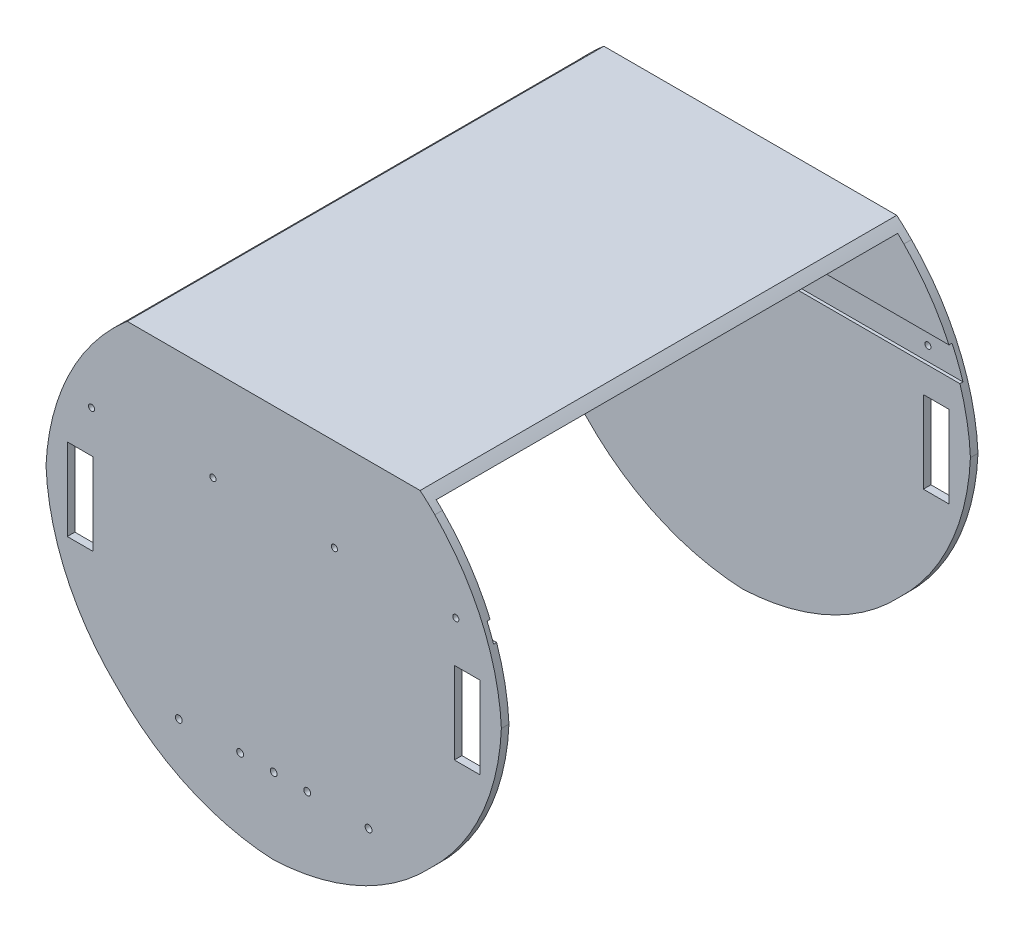
SolidWorks part; units mm, degrees
material "ABS"
ref_plane "Front Plane" through (0, 0, 0) normal (0, 0, 1) x (1, 0, 0)
ref_plane "Top Plane" through (0, 0, 0) normal (0, 1, 0) x (1, 0, 0)
ref_plane "Right Plane" through (0, 0, 0) normal (1, 0, 0) x (0, 0, -1)
sketch "Sketch1" plane through (0, 0, 0) normal (1, 0, 0) x (0, 0, -1)
  line L0 (-152, 0) -> (152, 0) construction
  line L1 (-152, 0) -> (-152, 254)
  line L2 (-152, 254) -> (152, 254)
  line L3 (152, 254) -> (152, 0)
  line L5 (-157, 0) -> (-157, 259)
  line L6 (-157, 259) -> (157, 259)
  line L7 (157, 259) -> (157, 0)
  line L8 (157, 0) -> (152, 0)
  line L10 (-152, 0) -> (-157, 0)
  point P4 (0, 0)
  dimension "D1" = 304
  dimension "D2" = 5
  dimension "D3" = 5
  dimension "D4" = 5
  dimension "D7" = 254
extrude "Boss-Extrude1" add sketch "Sketch1" along normal blind 150 and the other way blind 150
sketch "Sketch2" plane through (0, 0, 0) normal (0, 0, 1) x (1, 0, 0)
  line L1 (0, 150) -> (0, 0) construction
  line L2 (0, 150) -> (150, 150) construction
  line L3 (0, 150) -> (103.1245, 46.8755) construction
  line L4 (0, 150) -> (56.5109, 13.5707) construction
  line L5 (0, 150) -> (136.4293, 93.4891) construction
  line L6 (56.5109, 13.5707) -> (0, 13.5707) construction
  line L7 (136.4293, 93.4891) -> (136.4293, 150) construction
  line L8 (0, 150) -> (131.304, 216.3149) construction
  line L9 (0, 150) -> (0, 295.5) construction
  line L10 (0, 150) -> (106.1806, 249.9895) construction
  arc A0 (0, 0) -> (103.1245, 46.8755) centre (-6.3266, 150.7909) ccw
  arc A1 (150, 150) -> (103.1245, 46.8755) centre (-0.7909, 156.3266) cw
  arc A2 (106.1806, 249.9895) -> (150, 150) centre (-2.2818, 142.8605) cw
  arc A3 (106.1806, 249.9895) -> (0, 295.5) centre (-2.7988, 142.3499) ccw
  arc A4 (0, 0) -> (-103.1245, 46.8755) centre (6.3266, 150.7909) cw
  arc A5 (-150, 150) -> (-103.1245, 46.8755) centre (0.7909, 156.3266) ccw
  arc A6 (-106.1806, 249.9895) -> (-150, 150) centre (2.2818, 142.8605) ccw
  arc A7 (-106.1806, 249.9895) -> (0, 295.5) centre (2.7988, 142.3499) cw
  dimension "D1" = 150
  dimension "D2" = 22.5
  dimension "D3" = 22.5
  dimension "D4" = 145.84
  dimension "D5" = 147.67
  dimension "D6" = 147.1
  dimension "D7" = 26.796
  dimension "D8" = 145.5
  dimension "D9" = 43.28
  dimension "D10" = 145.85
extrude "Cut-Extrude1" cut sketch "Sketch2" against normal through all both and the other way through all flip side to cut contours A7 A6 A5 A4 A0 A1 A2 A3
sketch "Sketch3" plane through (0, 0, 0) normal (1, 0, 0) x (0, 0, -1)
  line L0 (-152, 198) -> (152, 198) construction
  line L1 (-154, 192.5) -> (-150, 192.5)
  line L2 (-154, 192.5) -> (-154, 203.5)
  line L3 (-154, 203.5) -> (-150, 203.5)
  line L4 (-150, 192.5) -> (-150, 203.5)
  line L5 (-154, 192.5) -> (-150, 203.5) construction
  line L6 (-154, 203.5) -> (-150, 192.5) construction
  line L7 (150, 188.75) -> (154, 188.75)
  line L8 (150, 188.75) -> (150, 207.25)
  line L9 (150, 207.25) -> (154, 207.25)
  line L10 (154, 188.75) -> (154, 207.25)
  line L11 (150, 188.75) -> (154, 207.25) construction
  line L12 (150, 207.25) -> (154, 188.75) construction
  line L13 (0, 0) -> (0, 198) construction
  point P0 (-152, 198)
  point P5 (152, 198)
  dimension "D1" = 304
  dimension "D2" = 4
  dimension "D3" = 198
  dimension "D4" = 11
extrude "Cut-Extrude2" cut sketch "Sketch3" against normal through all both and the other way through all
sketch "Sketch4" plane through (0, 0, 0) normal (0, 0, 1) x (1, 0, 0)
  line L0 (0, 0) -> (0, 259) construction
  line L1 (-96.4763, 259) -> (96.4763, 259) construction
  line L2 (-120, 198) -> (120, 198) construction
  circle A0 centre (-120, 198) radius 2
  circle A1 centre (120, 198) radius 2
  circle A2 centre (40, 198) radius 2
  circle A3 centre (-40, 198) radius 2
  point P8 (0, 198)
  dimension "D3" = 4
  dimension "D1" = 240
  dimension "D2" = 80
  dimension "D4" = 198
extrude "Cut-Extrude3" cut sketch "Sketch4" against normal through all both and the other way through all
sketch "Sketch6" plane through (0, 0, 0) normal (0, 0, 1) x (1, 0, 0)
  line L0 (-127.5, 143.5) -> (127.5, 143.5) construction
  line L1 (-136, 116.5) -> (-119, 116.5)
  line L2 (-136, 116.5) -> (-136, 170.5)
  line L3 (-136, 170.5) -> (-119, 170.5)
  line L4 (-119, 116.5) -> (-119, 170.5)
  line L5 (-136, 116.5) -> (-119, 170.5) construction
  line L6 (-136, 170.5) -> (-119, 116.5) construction
  line L7 (119, 170.5) -> (136, 170.5)
  line L8 (119, 170.5) -> (119, 116.5)
  line L9 (119, 116.5) -> (136, 116.5)
  line L10 (136, 170.5) -> (136, 116.5)
  line L11 (119, 170.5) -> (136, 116.5) construction
  line L12 (119, 116.5) -> (136, 170.5) construction
  line L13 (0, 143.5) -> (0, 0) construction
  point P0 (-127.5, 143.5)
  point P5 (127.5, 143.5)
  point P15 (127.5, 116.5)
  dimension "D1" = 272
  dimension "D2" = 17
  dimension "D3" = 54
  dimension "D4" = 116.5
extrude "Cut-Extrude4" cut sketch "Sketch6" against normal through all both and the other way through all
sketch "Sketch7" plane through (0, 0, 157) normal (0, 0, 1) x (1, 0, 0)
  line L0 (-22.11, 50) -> (22.11, 50) construction
  line L1 (62.5, 49.15) -> (-62.5, 49.15) construction
  line L2 (0, 50) -> (0, 49.15) construction
  line L3 (0, 0) -> (0, 49.15) construction
  circle A0 centre (0, 50) radius 2.25
  circle A1 centre (22.11, 50) radius 2.25
  circle A2 centre (-22.11, 50) radius 2.25
  circle A3 centre (-62.5, 49.15) radius 2.25
  circle A4 centre (62.5, 49.15) radius 2.25
  point P13 (0, 50)
  point P17 (0, 49.15)
  dimension "D1" = 4.5
  dimension "D2" = 4.5
  dimension "D3" = 22.11
  dimension "D4" = 62.5
  dimension "D5" = 0.85
  dimension "D6" = 100
extrude "Cut-Extrude5" cut sketch "Sketch7" against normal up to next
